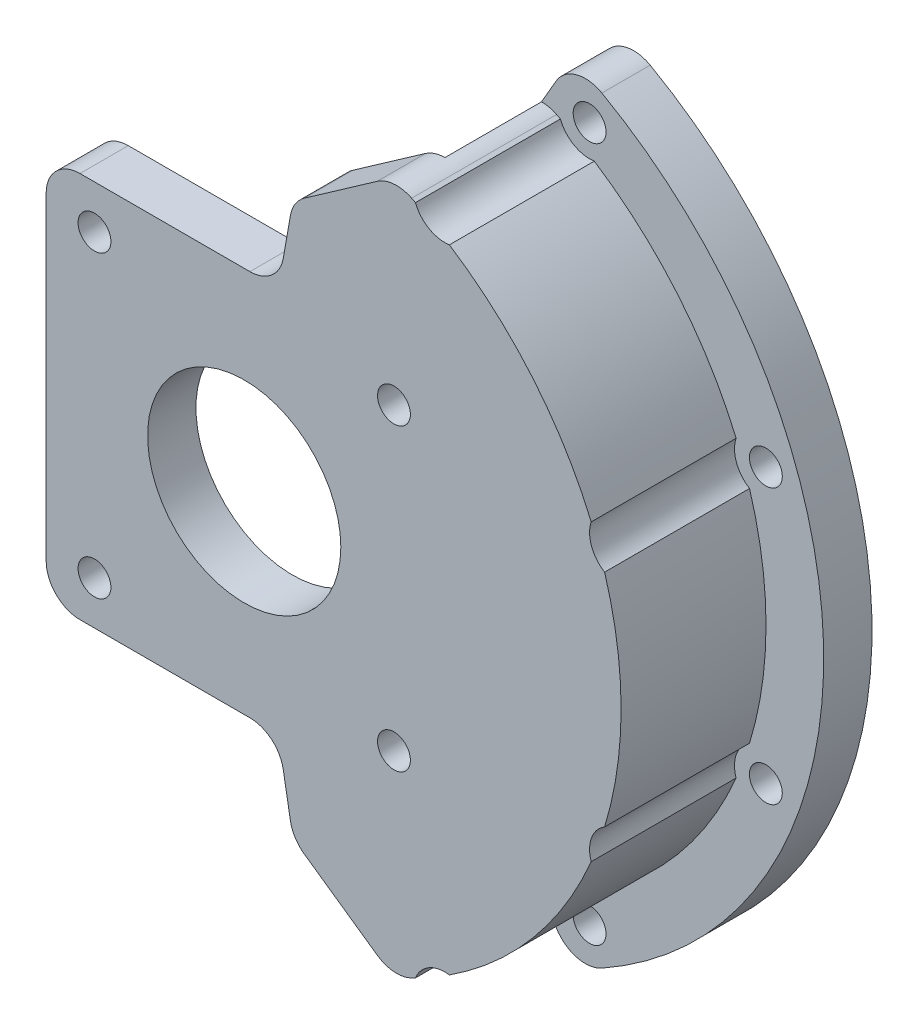
SolidWorks part; units mm, degrees
ref_plane "Alzado" through (0, 0, 0) normal (0, 0, 1) x (1, 0, 0)
ref_plane "Planta" through (0, 0, 0) normal (0, 1, 0) x (1, 0, 0)
ref_plane "Vista lateral" through (0, 0, 0) normal (1, 0, 0) x (0, 0, -1)
sketch "Croquis1" plane through (0, 0, 0) normal (0, 0, 1) x (1, 0, 0)
  line L0 (0, 0) -> (40.5, 0) construction
  line L1 (0, 0) -> (20.7522, 35.9388) construction
  line L2 (18.9417, 40.8027) -> (15.4414, 34.7407)
  line L3 (0, 0) -> (38.9981, 14.1915) construction
  line L4 (0, 0) -> (38.9964, -14.1962) construction
  line L5 (0, 0) -> (20.7478, -35.9413) construction
  line L6 (18.9417, -40.8027) -> (15.4414, -34.7407)
  circle A0 centre (0, 0) radius 40.5 construction
  circle A1 centre (20.7522, 35.9388) radius 1.7
  circle A2 centre (0, 0) radius 41.5 construction
  circle A3 centre (0, 0) radius 41.5 construction
  circle A4 centre (38.9981, 14.1915) radius 1.7
  circle A5 centre (0, 0) radius 41.5 construction
  circle A6 centre (38.9964, -14.1962) radius 1.7
  circle A7 centre (0, 0) radius 41.5 construction
  circle A8 centre (20.7478, -35.9413) radius 1.7
  arc A9 (15.4414, -34.7407) -> (15.4414, 34.7407) centre (0, 0) ccw
  arc A10 (18.9417, -40.8027) -> (18.9417, 40.8027) centre (0, 0) ccw
  point P9 (17.1915, 37.7717)
  point P22 (0, 0)
  dimension "D1" = 81
  dimension "D4" = 3.4
  dimension "D2" = 41.5
  dimension "D3" = 59.997
  dimension "D5" = 7
  dimension "D6" = 4
  dimension "D7" = 4
extrude "Saliente-Extruir1" add sketch "Croquis1" along normal blind 5
sketch "Croquis2" plane through (0, 0, 0) normal (0, 0, -1) x (-1, 0, 0)
  circle A0 centre (0, 0) radius 39.0124
extrude "Saliente-Extruir2" add sketch "Croquis2" against normal blind 20
sketch "Croquis3" plane through (0, 0, 20) normal (0, 0, 1) x (1, 0, 0)
  line L0 (0, 0) -> (-20.5, 0) construction
  line L1 (-15.5, -15.5) -> (15.5, -15.5) construction
  line L2 (-15.5, -15.5) -> (-15.5, 15.5) construction
  line L3 (-15.5, 15.5) -> (15.5, 15.5) construction
  line L4 (15.5, -15.5) -> (15.5, 15.5) construction
  line L5 (-15.5, -15.5) -> (15.5, 15.5) construction
  line L6 (-15.5, 15.5) -> (15.5, -15.5) construction
  line L7 (-20.5, 20) -> (-20.5, -20)
  line L8 (-20.5, 20) -> (3.5265, 20)
  line L9 (3.5265, 20) -> (6.7744, 38.4197)
  line L10 (3.5265, -20) -> (6.7744, -38.4197)
  line L11 (-20.5, -20) -> (3.5265, -20)
  circle A0 centre (-15.5, 15.5) radius 1.7
  circle A1 centre (15.5, 15.5) radius 1.7
  circle A2 centre (15.5, -15.5) radius 1.7
  circle A3 centre (-15.5, -15.5) radius 1.7
  circle A5 centre (0, 0) radius 39.0124 construction
  arc A6 (6.7744, 38.4197) -> (6.7744, -38.4197) centre (0, 0) ccw
  circle A7 centre (0, 0) radius 10
  point P0 (0, 0)
  point P16 (0, 0)
  point P18 (-20.5, 0)
  dimension "D3" = 3.4
  dimension "D6" = 20
  dimension "D2" = 31
  dimension "D4" = 40
  dimension "D5" = 20.5
  dimension "D7" = 100
  dimension "D1" = 4
extrude "Cortar-Extruir1" cut sketch "Croquis3" against normal blind 5
sketch "Croquis4" plane through (0, 0, 0) normal (0, 0, -1) x (-1, 0, 0)
  line L0 (-18.9417, 40.8027) -> (-15.9414, 35.6067)
  line L1 (-15.9414, 35.6067) -> (-13.9232, 32.1115)
  line L2 (0, 0) -> (35, 0) construction
  line L3 (-15.9414, -35.6067) -> (-13.9232, -32.1115)
  line L4 (-18.9417, -40.8027) -> (-15.9414, -35.6067)
  arc A0 (-13.9232, 32.1115) -> (-13.9232, -32.1115) centre (0, 0) ccw
  arc A1 (-18.9417, -40.8027) -> (-18.9417, 40.8027) centre (0, 0) ccw
  dimension "D1" = 70
extrude "Cortar-Extruir2" cut sketch "Croquis4" against normal blind 15
chamfer "Chaflán1" distance 10 angle 45 2 edges at (6.7744, 38.4197, 17.5) (6.7744, -38.4197, 17.5)
fillet "Redondeo2" radius 3.5 10 edges at (18.9417, -40.8027, 2.5) (18.9417, 40.8027, 2.5) (3.5265, 20, 17.5) (3.5265, -20, 17.5) (-20.5, -20, 17.5) (-20.5, 20, 17.5) (15.415, 35.8377, 17.5) (15.415, -35.8377, 17.5) (5.0379, -28.5716, 17.5) (5.0379, 28.5716, 17.5)
sketch "Croquis5" plane through (0, 0, 5) normal (0, 0, 1) x (1, 0, 0)
  circle A0 centre (20.7478, -35.9413) radius 3.25
  dimension "D1" = 6.5
extrude "Cortar-Extruir3" cut sketch "Croquis5" along normal up to surface (15 mm away) up to face at (-13.8, -15.5, 20)
pattern_circular "MatrizC1" count 4 over 120 about axis through (0, 0, 20) along (0, 0, -1) of "Cortar-Extruir3" reverse direction yes
sketch "Croquis6" plane through (0, 0, 15) normal (0, 0, -1) x (-1, 0, 0)
  circle A0 centre (15.5, 15.5) radius 3.25
  circle A1 centre (15.5, -15.5) radius 3.25
  circle A2 centre (-15.5, -15.5) radius 3.25
  circle A3 centre (-15.5, 15.5) radius 3.25
  point P12 (0, 0)
  dimension "D1" = 6.5
  dimension "D2" = 4
extrude "Cortar-Extruir4" cut sketch "Croquis6" against normal blind 2.5
chamfer "Chaflán4" distance 2 angle 45 1 edges at (35, 0, 15)
